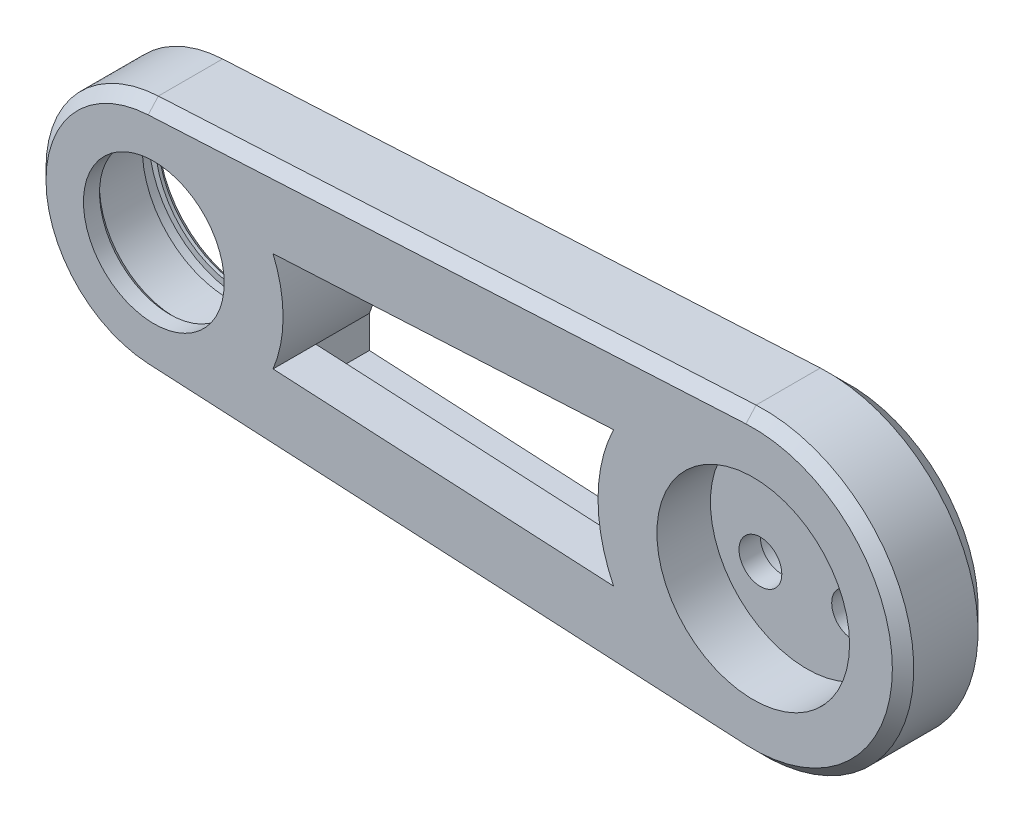
SolidWorks part; units mm, degrees
material "PEI"
ref_plane "前视基准面" through (0, 0, 0) normal (0, 0, 1) x (1, 0, 0)
ref_plane "上视基准面" through (0, 0, 0) normal (0, 1, 0) x (1, 0, 0)
ref_plane "右视基准面" through (0, 0, 0) normal (1, 0, 0) x (0, 0, -1)
other "Configuration Table"
sketch "草图2" plane through (0, 0, 0) normal (0, 0, 1) x (1, 0, 0)
  line L0 (0, 0) -> (56, 0) construction
  line L1 (-0.5785, 11.0599) -> (55.2687, 13.9809)
  line L2 (-0.5785, -11.0599) -> (55.2687, -13.9809)
  circle A0 centre (56, 0) radius 9
  circle A1 centre (56, 0) radius 14
  circle A2 centre (0, 0) radius 8.075
  circle A3 centre (0, 0) radius 11.075
  dimension "D1" = 18
  dimension "D2" = 28
  dimension "D4" = 16.15
  dimension "D3" = 56
  dimension "D5" = 3
extrude "凸台-拉伸1" add sketch "草图2" against normal blind 7 contours A2 A3 | A3 L0 A1 L1 | L0 A3 L2 A1 | A1 A0 region at (7.4083, -7.8059, 0) region at (27.1479, 6.7711, 0) region at (27.1479, -6.7711, 0) region at (46.1325, 9.3649, 0)
sketch "草图3" plane through (0, 0, -7) normal (0, 0, -1) x (-1, 0, 0)
  line L2 (-55.2687, -13.9809) -> (0.5785, -11.0599)
  line L3 (0.5785, 11.0599) -> (-55.2687, 13.9809)
  line L4 (-55.2687, -13.9809) -> (0.5785, -11.0599)
  line L5 (0.5785, 11.0599) -> (-55.2687, 13.9809)
  circle A0 centre (-56, 0) radius 9 construction
  circle A1 centre (-56, 0) radius 9
  arc A2 (0.5785, -11.0599) -> (0.5785, 11.0599) centre (0, 0) ccw
  arc A3 (-55.2687, 13.9809) -> (-55.2687, -13.9809) centre (-56, 0) ccw
  arc A4 (0.5785, -11.0599) -> (0.5785, 11.0599) centre (0, 0) ccw
  arc A5 (-55.2687, 13.9809) -> (-55.2687, -13.9809) centre (-56, 0) ccw
  circle A6 centre (0, 0) radius 8.075 construction
  circle A7 centre (0, 0) radius 8.075
  line M5 (-55.2687, -13.9809) -> (0.5785, -11.0599)
  arc M6 (0.5785, -11.0599) -> (0.5785, 11.0599) centre (0, 0) ccw
  line M7 (0.5785, 11.0599) -> (-55.2687, 13.9809)
  arc M8 (-55.2687, 13.9809) -> (-55.2687, -13.9809) centre (-56, 0) ccw
  circle M9 centre (0, 0) radius 8.075
  circle M10 centre (-56, 0) radius 9
  dimension "D1" = 0
extrude "凸台-拉伸2" add sketch "草图3" along normal blind 3 contours M10 | M8 M5 M6 M7 M9 M10 region at (30.9645, 0, -7) region at (56, 0, -7)
sketch "草图4" plane through (0, 0, 0) normal (0, 0, 1) x (1, 0, 0)
  circle A0 centre (0, 0) radius 8.075 construction
  circle A1 centre (0, 0) radius 8.075
  circle A2 centre (0, 0) radius 6.575
  dimension "D1" = 1.5
extrude "凸台-拉伸3" add sketch "草图4" against normal blind 3
chamfer "倒角1" distance 0.5 angle 45 4 edges at (65, 0, 0) (-8.075, 0, -10) (6.575, 0, -3) (6.575, 0, 0)
chamfer "倒角2" distance 2 angle 45 8 edges at (27.3451, -12.5204, -10) (-11.075, 0, -10) (70, 0, -10) (27.3451, 12.5204, -10) (27.3451, -12.5204, 0) (-11.075, 0, 0) (70, 0, 0) (27.3451, 12.5204, 0)
sketch "草图5" plane through (0, 0, -10) normal (0, 0, -1) x (-1, 0, 0)
  line L0 (-85.5329, 0) -> (49.23, 0) construction
  line L1 (-56, 18.9424) -> (-56, -22.3961) construction
  circle A0 centre (-56, 0) radius 5 construction
  circle A1 centre (-56, 0) radius 9
  circle A2 centre (-56, 0) radius 9
  circle A3 centre (-56, 5) radius 2
  circle A7 centre (-51.6699, -2.5) radius 2
  circle A8 centre (-60.3301, -2.5) radius 2
  dimension "D2" = 10
  dimension "D3" = 4
  dimension "D1" = 0
extrude "切除-拉伸1" cut sketch "草图5" against normal up to surface (3 mm away) contours A3 | A8 | A7 region at (56, 5, -10) region at (51.6699, -2.5, -10) region at (60.3301, -2.5, -10) up to face at (65, 0, -7)
sketch "草图6" plane through (0, 0, 0) normal (0, 0, 1) x (1, 0, 0)
  line L0 (55.6344, 6.9904) -> (-0.2128, 4.0694)
  line L1 (-0.2128, -4.0694) -> (55.6344, -6.9904)
  line L2 (-0.474, -9.0626) -> (55.3732, -11.9836)
  line L3 (55.3732, 11.9836) -> (-0.474, 9.0626)
  line L4 (-0.474, -9.0626) -> (55.3732, -11.9836)
  line L5 (55.3732, 11.9836) -> (-0.474, 9.0626)
  circle A0 centre (0, 0) radius 7.075 construction
  circle A1 centre (0, 0) radius 7.075
  arc A2 (-0.474, 9.0626) -> (-0.474, -9.0626) centre (0, 0) ccw
  arc A3 (55.3732, -11.9836) -> (55.3732, 11.9836) centre (56, 0) ccw
  arc A4 (-0.474, 9.0626) -> (-0.474, -9.0626) centre (0, 0) ccw
  arc A5 (55.3732, -11.9836) -> (55.3732, 11.9836) centre (56, 0) ccw
  circle A6 centre (56, 0) radius 9.5 construction
  circle A7 centre (56, 0) radius 9.5
  arc A9 (-0.2128, 4.0694) -> (-0.2128, -4.0694) centre (0, 0) ccw
  arc A10 (55.6344, -6.9904) -> (55.6344, 6.9904) centre (56, 0) ccw
  circle A12 centre (0, 0) radius 12.075
  circle A13 centre (56, 0) radius 14.5
  dimension "D1" = 0
  dimension "D2" = 5
  dimension "D3" = 5
extrude "切除-拉伸2" cut sketch "草图6" against normal up to surface (10 mm away) contours A13 L0 A12 L1 region at (27.5952, 0, 0) up to face at (54, 5, -10)
sketch "草图7" plane through (0, 0, -10) normal (0, 0, -1) x (-1, 0, 0)
  line L0 (-11.1383, -4.6631) -> (-42.9533, -6.3272) construction
  line L1 (-42.9533, 6.3272) -> (-11.1383, 4.6631) construction
  line L2 (-11.1383, -4.6631) -> (-42.9533, -6.3272)
  line L3 (-42.9533, 6.3272) -> (-11.1383, 4.6631)
  line L4 (-42.9533, 9.3313) -> (-11.1383, 7.6672)
  line L5 (-42.9533, -9.3313) -> (-11.1383, -7.6672)
  line L6 (-42.9533, -9.3313) -> (-42.9533, -6.3272)
  line L7 (-11.1383, -7.6672) -> (-11.1383, -4.6631)
  line L8 (-11.1383, 7.6672) -> (-11.1383, 4.6631)
  line L9 (-42.9533, 9.3313) -> (-42.9533, 6.3272)
  line M5 (-42.9533, 6.3272) -> (-11.1383, 4.6631)
  line M7 (-11.1383, -4.6631) -> (-42.9533, -6.3272)
  dimension "D1" = 3
  dimension "D2" = 3
extrude "切除-拉伸3" cut sketch "草图7" against normal blind 5 contours L4 L9 L8 M5 | L5 L7 L6 M7 region at (27.0458, -6.9972, -10) region at (27.0458, 6.9972, -10)
sketch "草图8" plane through (0, 0, 0) normal (0, 1, 0) x (1, 0, 0)
  line L0 (8.075, 3) -> (-8.075, 3) construction
  line L1 (8.075, 3) -> (-8.075, 3)
  line L2 (0, 3) -> (0, 12.4647) construction
  line L4 (8.075, 8) -> (8.65, 8)
  line L5 (8.65, 8) -> (8.65, 9.2)
  line L6 (8.65, 9.2) -> (8.075, 9.2)
  line L7 (8.075, 9.2) -> (8.075, 8)
  dimension "D1" = 1.2
  dimension "D2" = 5
  dimension "D3" = 8.075
  dimension "D4" = 8.65
revolve "切除-旋转1" cut sketch "草图8" angle 360 about L2 region at (8.3625, 0, -8.6)
sketch "草图9" plane through (0, 0, 0) normal (0, 0, 1) x (1, 0, 0)
  line L0 (55.2687, -13.9809) -> (-0.5785, -11.0599) construction
  line L1 (-0.5785, 11.0599) -> (55.2687, 13.9809) construction
  line L2 (55.2687, -13.9809) -> (-0.5785, -11.0599)
  line L3 (-0.5785, 11.0599) -> (55.2687, 13.9809)
  arc A0 (55.2687, -13.9809) -> (55.2687, 13.9809) centre (56, 0) ccw construction
  arc A1 (-0.5785, 11.0599) -> (-0.5785, -11.0599) centre (0, 0) ccw construction
  arc A2 (55.2687, -13.9809) -> (55.2687, 13.9809) centre (56, 0) ccw
  arc A3 (-0.5785, 11.0599) -> (-0.5785, -11.0599) centre (0, 0) ccw
extrude "切除-拉伸4" cut sketch "草图9" against normal blind 1
sketch "草图10" plane through (0, 0, -7) normal (0, 0, 1) x (1, 0, 0)
  circle A0 centre (56, 5) radius 2 construction
  circle A1 centre (56, 0) radius 9
  circle A2 centre (56, 0) radius 9
  circle A3 centre (56, 5) radius 2
  circle A4 centre (51.6699, -2.5) radius 2 construction
  circle A5 centre (51.6699, -2.5) radius 2
  circle A6 centre (60.3301, -2.5) radius 2 construction
  circle A7 centre (60.3301, -2.5) radius 2
  circle M3 centre (56, 5) radius 2
  circle M4 centre (60.3301, -2.5) radius 2
  circle M5 centre (51.6699, -2.5) radius 2
  circle M6 centre (56, 0) radius 9
  dimension "D1" = 0
extrude "凸台-拉伸4" add sketch "草图10" along normal blind 1 contours M6 M4 M5 M3 region at (56, 0, -7)
sketch "草图11" plane through (0, 0, -10) normal (0, 0, -1) x (-1, 0, 0)
  circle A0 centre (-51.6699, -2.5) radius 2 construction
  circle A1 centre (-60.3301, -2.5) radius 2 construction
  circle A2 centre (-56, 5) radius 2 construction
  circle A3 centre (-51.6699, -2.5) radius 2
  circle A4 centre (-60.3301, -2.5) radius 2
  circle A5 centre (-56, 5) radius 2
  circle A6 centre (-56, 5) radius 2.85
  circle A7 centre (-60.3301, -2.5) radius 2.85
  circle A8 centre (-51.6699, -2.5) radius 2.85
  dimension "D1" = 5.7
  dimension "D2" = 5.7
  dimension "D3" = 5.7
extrude "切除-拉伸5" cut sketch "草图11" against normal blind 2
equation "\"D3@草图2\"= \"从动杆_后_长度\""
equation "\"从动杆_后_长度\"= 56"
